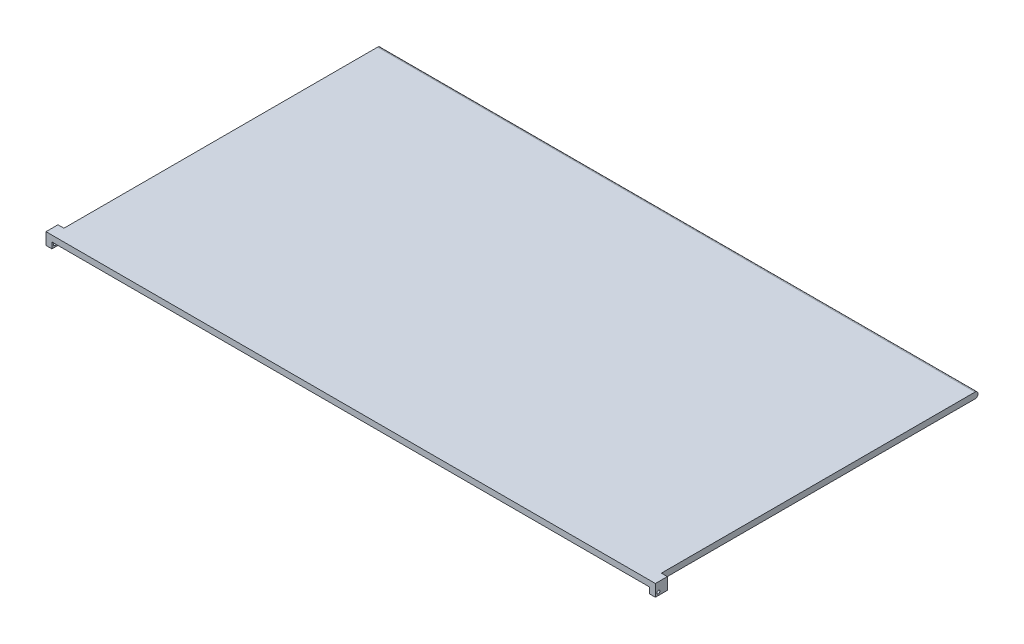
SolidWorks part; units mm, degrees
ref_plane "Front Plane" through (0, 0, 0) normal (0, 0, 1) x (1, 0, 0)
ref_plane "Top Plane" through (0, 0, 0) normal (0, 1, 0) x (1, 0, 0)
ref_plane "Right Plane" through (0, 0, 0) normal (1, 0, 0) x (0, 0, -1)
sketch "Sketch1" plane through (0, 0, 0) normal (0, 1, 0) x (1, 0, 0)
  line L1 (100, -55) -> (-100, -55)
  line L2 (100, -55) -> (100, 55)
  line L3 (100, 55) -> (-100, 55)
  line L4 (-100, -55) -> (-100, 55)
  line L5 (100, -55) -> (-100, 55) construction
  line L6 (100, 55) -> (-100, -55) construction
  point P0 (0, 0)
  dimension "D1" = 200
  dimension "D2" = 110
extrude "Boss-Extrude1" add sketch "Sketch1" along normal blind 2
fillet "Fillet1" radius 1 2 edges at (0, 0, -55) (0, 2, -55)
sketch "Sketch3" plane through (-100, 0, 0) normal (-1, 0, 0) x (0, 0, 1)
  line L1 (55, 2) -> (51, 2)
  line L2 (55, 2) -> (55, -2)
  line L3 (55, -2) -> (51, -2)
  line L4 (51, 2) -> (51, -2)
  circle A0 centre (54, -1.0035) radius 0.5
  dimension "D3" = 1
  dimension "D1" = 4
  dimension "D2" = 4
  dimension "D4" = 1
  dimension "D5" = 0.9965
extrude "Boss-Extrude2" add sketch "Sketch3" along normal blind 2
sketch "Sketch4" plane through (100, 0, 0) normal (1, 0, 0) x (0, 0, -1)
  line L1 (-51, -2) -> (-55, -2)
  line L2 (-51, -2) -> (-51, 2)
  line L3 (-51, 2) -> (-55, 2)
  line L4 (-55, -2) -> (-55, 2)
  circle A0 centre (-54, -1.0035) radius 0.5
extrude "Boss-Extrude3" add sketch "Sketch4" along normal blind 2
